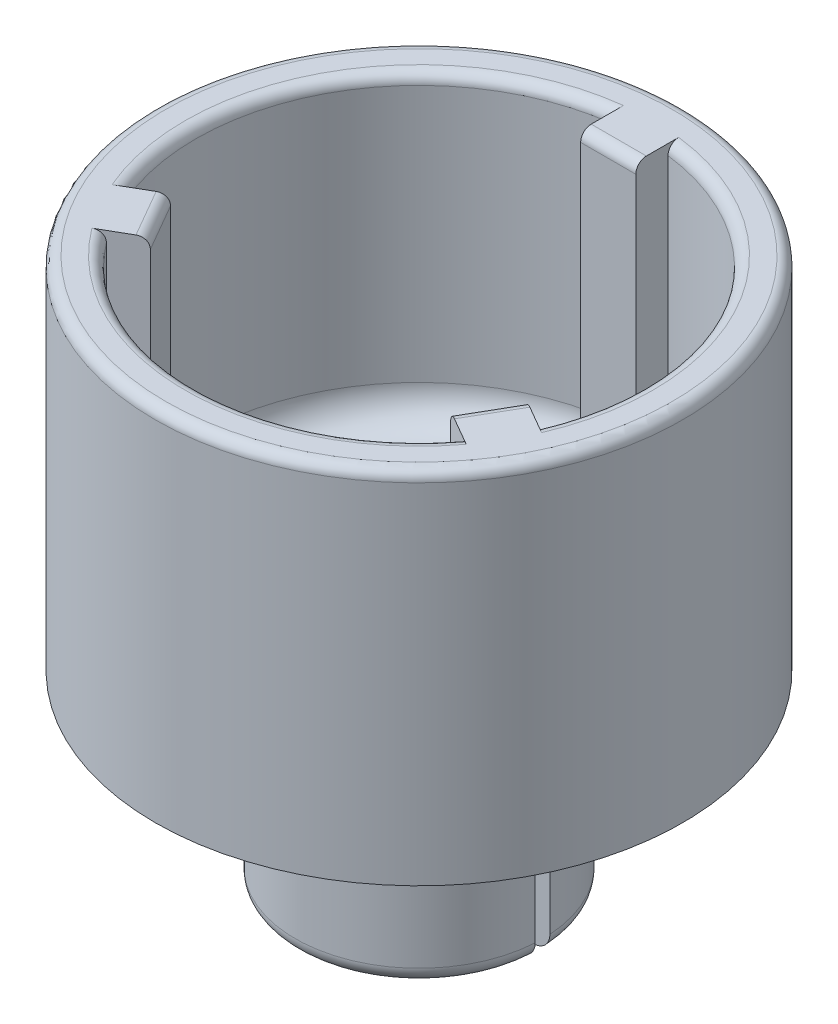
SolidWorks part; units mm, degrees
ref_plane "Front Plane" through (0, 0, 0) normal (0, 0, 1) x (1, 0, 0)
ref_plane "Top Plane" through (0, 0, 0) normal (0, 1, 0) x (1, 0, 0)
ref_plane "Right Plane" through (0, 0, 0) normal (1, 0, 0) x (0, 0, -1)
sketch "Sketch1" plane through (0, 0, 0) normal (0, 1, 0) x (1, 0, 0)
  circle A0 centre (0, 0) radius 32.5
  dimension "D1" = 65
extrude "Boss-Extrude1" add sketch "Sketch1" along normal blind 44.3
sketch "Sketch2" plane through (0, 44.3, 0) normal (0, 1, 0) x (1, 0, 0)
  circle A0 centre (0, 0) radius 27.5
  dimension "D1" = 55
extrude "Cut-Extrude1" cut sketch "Sketch2" against normal blind 37
sketch "Sketch3" plane through (0, 0, 0) normal (0, -1, 0) x (1, 0, 0)
  circle A0 centre (0, 0) radius 19.5
  dimension "D1" = 39
extrude "Boss-Extrude2" add sketch "Sketch3" along normal blind 7
sketch "Sketch4" plane through (0, -7, 0) normal (0, -1, 0) x (1, 0, 0)
  circle A0 centre (0, 0) radius 15.25
  dimension "D1" = 30.5
extrude "Boss-Extrude3" add sketch "Sketch4" along normal blind 16
fillet "Fillet1" radius 6 1 edges at (0, 0, -19.5)
sketch "Sketch7" plane through (0, -23, 0) normal (0, -1, 0) x (1, 0, 0)
  line L1 (33.0968, 0.9034) -> (-33.0968, 0.9034)
  line L2 (33.0968, 0.9034) -> (33.0968, -0.9034)
  line L3 (33.0968, -0.9034) -> (-33.0968, -0.9034)
  line L4 (-33.0968, 0.9034) -> (-33.0968, -0.9034)
  line L5 (33.0968, 0.9034) -> (-33.0968, -0.9034) construction
  line L6 (33.0968, -0.9034) -> (-33.0968, 0.9034) construction
  point P0 (0, 0)
extrude "Cut-Extrude2" cut sketch "Sketch7" against normal up to surface (16 mm away) up to face at (0, -7, -15.25)
fillet "Fillet2" radius 2 2 edges at (0, -23, 15.25) (0, -23, -15.25)
sketch "Sketch9" plane through (0, 7.3, 0) normal (0, 1, 0) x (1, 0, 0)
  circle A0 centre (0, 0) radius 7.5
  dimension "D1" = 15
extrude "Cut-Extrude3" cut sketch "Sketch9" against normal through all
sketch "Sketch11" plane through (0, 44.3, 0) normal (0, 1, 0) x (1, 0, 0)
  line L0 (0, 0) -> (0, -50000) construction
  line L6 (3.4, 32.3217) -> (-3.4, 32.3217)
  line L7 (3.4, 32.3217) -> (3.4, 23.3217)
  line L8 (3.4, 23.3217) -> (-3.4, 23.3217)
  line L9 (-3.4, 32.3217) -> (-3.4, 23.3217)
  circle A2 centre (0, 0) radius 32.5 construction
  dimension "D1" = 6.8
  dimension "D2" = 9
extrude "Boss-Extrude4" add sketch "Sketch11" against normal up to next
pattern_circular "CirPattern1" count 3 over 360 about axis through (0, 44.3, 0) along (0, 1, 0) of "Boss-Extrude4"
fillet "Fillet3" radius 1.3 7 edges at (20.1972, 44.3, 11.6608) (0, 44.3, -23.3217) (-20.1972, 44.3, 11.6608) (0, 44.3, 32.5) (23.8157, 44.3, -13.75) (0, 44.3, 27.5) (-23.8157, 44.3, -13.75)
fillet "Fillet4" radius 4 3 edges at (23.8157, 7.3, -13.75) (-23.8157, 7.3, -13.75) (0, 7.3, 27.5)
fillet "Fillet7" radius 3 1 edges at (0, 7.3, 7.5)
